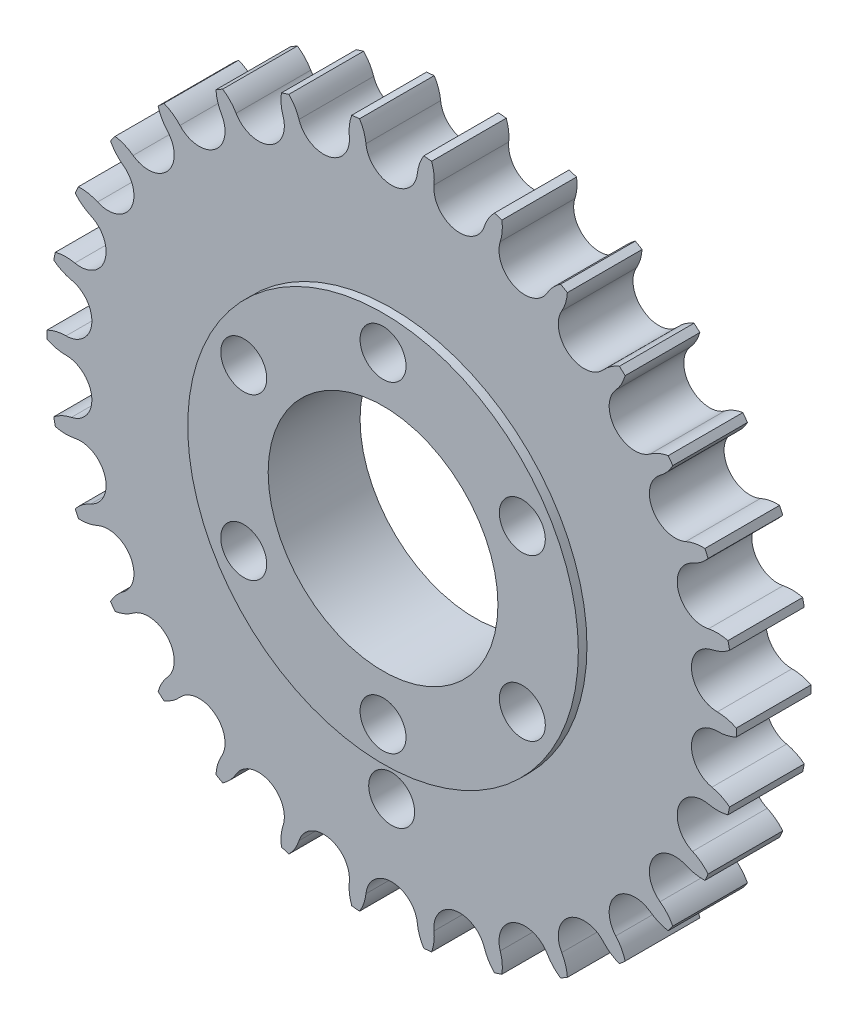
SolidWorks part; units mm, degrees
ref_plane "Front Plane" through (0, 0, 0) normal (0, 0, 1) x (1, 0, 0)
ref_plane "Top Plane" through (0, 0, 0) normal (0, 1, 0) x (1, 0, 0)
ref_plane "Right Plane" through (0, 0, 0) normal (1, 0, 0) x (0, 0, -1)
sketch "Sketch2" plane through (0, 0, 0) normal (0, 0, 1) x (1, 0, 0)
  circle A0 centre (0, 0) radius 30
  circle A1 centre (0, 0) radius 10
  dimension "D1" = 60
  dimension "D2" = 20
extrude "Boss-Extrude1" add sketch "Sketch2" along normal mid plane 8
sketch "Sketch3" plane through (0, 0, 4) normal (0, 0, 1) x (1, 0, 0)
  circle A2 centre (0, 0) radius 17
  circle A3 centre (0, 0) radius 17
  dimension "D1" = 7
extrude "Cut-Extrude1" cut sketch "Sketch3" against normal mid plane 1.5 flip side to cut
sketch "Sketch4" plane through (0, 0, -4) normal (0, 0, -1) x (-1, 0, 0)
  circle A0 centre (0, 0) radius 30 construction
  circle A2 centre (0, 0) radius 30
  circle A4 centre (0, 0) radius 17 construction
  circle A5 centre (0, 0) radius 17
extrude "Cut-Extrude2" cut sketch "Sketch4" against normal mid plane 1.5
sketch "Sketch5" plane through (0, 0, 0) normal (0, 0, 1) x (1, 0, 0)
  line L0 (0, 0) -> (0, 28.5) construction
  line L1 (0, 28.5) -> (5.9255, 27.8772) construction
  line L2 (5.9255, 27.8772) -> (0, 0) construction
  line L3 (-5.9255, 27.8772) -> (0, 0) construction
  circle A0 centre (0, 28.5) radius 3.7081
  circle A1 centre (5.9255, 27.8772) radius 3.7081
  circle A2 centre (5.9255, 27.8772) radius 2.25
  circle A3 centre (0, 28.5) radius 2.25
  circle A4 centre (-5.9255, 27.8772) radius 3.7081
  circle A5 centre (-5.9255, 27.8772) radius 2.25
  dimension "D3" = 4.5
  dimension "D1" = 28.5
  dimension "D2" = 12
extrude "Cut-Extrude3" cut sketch "Sketch5" against normal mid plane 10 contours A3 | A0 A4 A3 A1 region at (0, 30.8552, 0) region at (0, 28.5, 0)
pattern_circular "CirPattern1" count 30 over 360 about axis through (0, 0, -4) along (0, 0, 1) of "Cut-Extrude3"
sketch "Sketch6" plane through (0, 0, 0) normal (0, 0, 1) x (1, 0, 0)
  circle A0 centre (0, 14) radius 2
  circle A1 centre (12.1244, 7) radius 2
  circle A2 centre (12.1244, -7) radius 2
  circle A3 centre (0, -14) radius 2
  circle A4 centre (-12.1244, -7) radius 2
  circle A5 centre (-12.1244, 7) radius 2
  point P15 (0, 0)
  dimension "D1" = 14
  dimension "D2" = 4
  dimension "D3" = 6
extrude "Cut-Extrude4" cut sketch "Sketch6" against normal mid plane 10
sketch "Sketch7" plane through (0, 0, -3.25) normal (0, 0, -1) x (-1, 0, 0)
  circle A0 centre (0, 0) radius 23
  circle A1 centre (0, 0) radius 17 construction
  circle A2 centre (0, 0) radius 17
  dimension "D1" = 46
extrude "Cut-Extrude5" cut sketch "Sketch7" against normal mid plane 1
sketch "Sketch8" plane through (0, 0, -2.75) normal (0, 0, -1) x (-1, 0, 0)
  circle A0 centre (0, -20) radius 2
  point P2 (0, 0)
  dimension "D1" = 4
  dimension "D2" = 20
extrude "Cut-Extrude6" cut sketch "Sketch8" against normal blind 10
